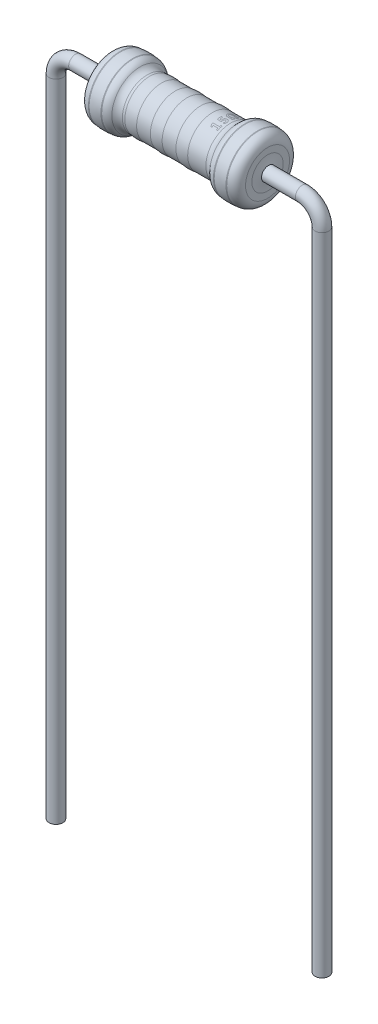
SolidWorks part; units mm, degrees
material "Plain Carbon Steel"
ref_plane "Front Plane" through (0, 0, 0) normal (0, 0, 1) x (1, 0, 0)
ref_plane "Top Plane" through (0, 0, 0) normal (0, 1, 0) x (1, 0, 0)
ref_plane "Right Plane" through (0, 0, 0) normal (1, 0, 0) x (0, 0, -1)
sketch "Sketch1" plane through (0, 0, 0) normal (0, 0, 1) x (1, 0, 0)
  line L0 (-4.33, 0) -> (4.33, 0)
  line L1 (-5.08, -0.75) -> (-5.08, -25.4)
  line L2 (5.08, -0.75) -> (5.08, -25.4)
  line L3 (-5.08, -25.4) -> (5.08, -25.4) construction
  line L4 (0, 0) -> (0, -25.4) construction
  arc A0 (-4.33, 0) -> (-5.08, -0.75) centre (-4.33, -0.75) ccw
  arc A1 (4.33, 0) -> (5.08, -0.75) centre (4.33, -0.75) cw
  dimension "D2" = 0.75
  dimension "D1" = 10.16
  dimension "D3" = 25.4
ref_plane "Plane1" through (-5.08, -25.4, 0) normal (0, -1, 0) x (-1, 0, 0)
sketch "Sketch2" plane through (-5.08, -25.4, 0) normal (0, -1, 0) x (-1, 0, 0)
  circle A0 centre (0, 0) radius 0.265
  dimension "D1" = 0.53
sweep "Sweep1" add profiles "Sketch2" path "Sketch1"
sketch "Sketch3" plane through (0, 0, 0) normal (0, 0, 1) x (1, 0, 0)
  line L0 (-3, 0) -> (3, 0)
  line L5 (-3, 0) -> (-3, 1.2)
  line L6 (3, 0) -> (3, 1.2)
  line L7 (-3, 1.2) -> (-1.8, 1.2)
  line L8 (3, 1.2) -> (1.8, 1.2)
  line L9 (-1.8, 1.2) -> (-1.8, 0.95)
  line L10 (-1.8, 0.95) -> (1.8, 0.95)
  line L11 (1.8, 0.95) -> (1.8, 1.2)
  line L12 (0, 0) -> (0, 0.95) construction
  dimension "D1" = 6
  dimension "D2" = 1.2
  dimension "D3" = 3.6
  dimension "D4" = 0.95
  dimension "D5" = 0.25
revolve "Revolve1" add sketch "Sketch3" angle 360 about L0
fillet "Fillet-1" radius 0.35 2 edges at (1.8, 0, 1.2) (-1.8, 0, 1.2)
fillet "Fillet-2" radius 0.36 4 edges at (3, 0, 1.2) (-3, 0, 1.2) (1.8, 0, 0.95) (-1.8, 0, 0.95)
sketch "Sketch5" plane through (0, 0, 0) normal (0, 0, 1) x (1, 0, 0)
  line L0 (-2.64, -1.2) -> (-2.1354, -1.2) construction
  line L5 (-2.3877, -1.2) -> (-2.3877, 0) construction
  line L10 (-3, 1.2) -> (-1.8, 1.2) construction
  line L15 (-1.05, 0.95) -> (-0.525, 0.95) construction
  line L16 (-3, 0) -> (3, 0) construction
  line L17 (-2.6127, 1.2) -> (-2.1627, 1.2) construction
  line L18 (-2.6127, 1.2) -> (-2.6127, 0) construction
  line L19 (-2.6127, 0) -> (-2.1627, 0) construction
  line L20 (-2.1627, 1.2) -> (-2.1627, 0) construction
  line L21 (-1.8, 0.95) -> (1.8, 0.95) construction
  line L22 (2.6127, 1.2) -> (2.1627, 1.2) construction
  line L23 (2.6127, 1.2) -> (2.6127, 0) construction
  line L24 (2.6127, 0) -> (2.1627, 0) construction
  line L25 (2.1627, 1.2) -> (2.1627, 0) construction
  line L26 (-1.05, 0.95) -> (-1.5, 0.95) construction
  line L27 (-1.05, 0.95) -> (-1.05, 0) construction
  line L28 (-1.05, 0) -> (-1.5, 0) construction
  line L29 (-1.5, 0.95) -> (-1.5, 0) construction
  line L30 (-2.3877, 1.2) -> (-2.3877, 1.22) construction
  line L31 (-0.075, 0.95) -> (-0.525, 0.95) construction
  line L32 (-0.075, 0.95) -> (-0.075, 0) construction
  line L33 (-0.075, 0) -> (-0.525, 0) construction
  line L34 (-0.525, 0.95) -> (-0.525, 0) construction
  line L35 (-1.275, 0.95) -> (-1.275, 0.97) construction
  line L36 (-0.3, 0.95) -> (-0.3, 0.97) construction
  line L37 (2.3877, 1.2) -> (2.3877, 1.22) construction
  line L39 (2.1354, -1.2) -> (2.64, -1.2) construction
  line L41 (2.3877, -1.2) -> (2.3877, 0) construction
  line L44 (3, 1.2) -> (1.8, 1.2) construction
  line L46 (-0.075, 0.95) -> (0.45, 0.95) construction
  line L48 (-3, 0) -> (-3, 0.6)
  line L49 (-3, 0) -> (-3, 1.2) construction
  line L50 (-3, 0) -> (-3.05, 0)
  line L51 (-3.05, 0) -> (-3.05, 0.2)
  line L52 (3, 0) -> (3.05, 0)
  line L53 (3.05, 0) -> (3.05, 0.2)
  line L54 (3, 0) -> (3, 0.6)
  line L55 (3, 0) -> (3, 1.2) construction
  line L56 (-1.05, 0) -> (-0.525, 0) construction
  line L58 (-0.075, 0) -> (0.45, 0) construction
  line L59 (0.45, 0) -> (0.45, 0.95) construction
  line L60 (0.45, 0) -> (0.9, 0) construction
  line L61 (0.9, 0) -> (0.9, 0.95) construction
  line L62 (1.5946, 0.95) -> (-1.5946, 0.95) construction
  line L63 (0.9, 0.95) -> (0.45, 0.95) construction
  line L64 (0.675, 0.95) -> (0.675, 0.97) construction
  arc A0 (-2.6127, 1.2) -> (-2.1627, 1.2) centre (-2.3877, -0.0556) cw construction
  arc A1 (-1.5, 0.95) -> (-1.05, 0.95) centre (-1.275, -0.3056) cw construction
  arc A2 (-0.525, 0.95) -> (-0.075, 0.95) centre (-0.3, -0.3056) cw construction
  arc A3 (2.1627, 1.2) -> (2.6127, 1.2) centre (2.3877, -0.0556) cw construction
  arc A6 (-3, 0.6) -> (-3.05, 0.2) centre (-4.625, 0.6) cw
  arc A7 (3.05, 0.2) -> (3, 0.6) centre (4.625, 0.6) cw
  arc A8 (0.45, 0.95) -> (0.9, 0.95) centre (0.675, -0.3056) cw construction
  dimension "D4" = 0.02
  dimension "D5" = 0.05
  dimension "D7" = 0.6
  dimension "D2" = 1.5
  dimension "D3" = 2.4
  dimension "D1" = 0.45
  dimension "D6" = 0.2
revolve "Revolve Ends" add sketch "Sketch5" angle 360 about L19
sketch "Sketch12" plane through (0, 0, 0) normal (0, 0, 1) x (1, 0, 0)
  line L0 (-2.6127, 0) -> (-2.1627, 0) construction
  line L1 (-2.6127, 0) -> (-2.1627, 0)
  line L2 (-2.6127, 1.2) -> (-2.6127, 0) construction
  line L3 (-2.6127, 1.2) -> (-2.6127, 0)
  line L4 (-2.1627, 1.2) -> (-2.1627, 0) construction
  line L5 (-2.1627, 1.2) -> (-2.1627, 0)
  arc A0 (-2.1627, 1.2) -> (-2.6127, 1.2) centre (-2.3877, -0.0556) ccw construction
  arc A1 (-2.1627, 1.2) -> (-2.6127, 1.2) centre (-2.3877, -0.0556) ccw
revolve "Revolve BAND 1" add sketch "Sketch12" angle 360 about L19
sketch "Sketch7" plane through (0, 0, 0) normal (0, 0, 1) x (1, 0, 0)
  line L0 (-1.05, 0) -> (-1.5, 0) construction
  line L1 (-1.05, 0.95) -> (-1.05, 0) construction
  line L2 (-1.5, 0.95) -> (-1.5, 0) construction
  line L3 (-1.05, 0.95) -> (-1.05, 0)
  line L4 (-1.5, 0.95) -> (-1.5, 0)
  line L5 (-1.05, 0) -> (-1.5, 0)
  arc A0 (-1.05, 0.95) -> (-1.5, 0.95) centre (-1.275, -0.3056) ccw construction
  arc A1 (-1.05, 0.95) -> (-1.5, 0.95) centre (-1.275, -0.3056) ccw
revolve "Revolve BAND 2" add sketch "Sketch7" angle 360 about L28
sketch "Sketch8" plane through (0, 0, 0) normal (0, 0, 1) x (1, 0, 0)
  line L0 (-0.075, 0.95) -> (-0.075, 0) construction
  line L1 (-0.075, 0) -> (-0.525, 0) construction
  line L2 (-0.525, 0.95) -> (-0.525, 0) construction
  line L3 (-0.075, 0.95) -> (-0.075, 0)
  line L4 (-0.075, 0) -> (-0.525, 0)
  line L5 (-0.525, 0.95) -> (-0.525, 0)
  arc A0 (-0.075, 0.95) -> (-0.525, 0.95) centre (-0.3, -0.3056) ccw construction
  arc A1 (-0.075, 0.95) -> (-0.525, 0.95) centre (-0.3, -0.3056) ccw
revolve "Revolve BAND 3" add sketch "Sketch8" angle 360 about L33
sketch "Sketch9" plane through (0, 0, 0) normal (0, 0, 1) x (1, 0, 0)
  line L0 (0.9, 0) -> (0.9, 0.95) construction
  line L1 (0.45, 0) -> (0.45, 0.95) construction
  line L2 (0.45, 0) -> (0.9, 0) construction
  line L3 (0.9, 0) -> (0.9, 0.95)
  line L4 (0.45, 0) -> (0.45, 0.95)
  line L5 (0.45, 0) -> (0.9, 0)
  arc A0 (0.9, 0.95) -> (0.45, 0.95) centre (0.675, -0.3056) ccw construction
  arc A1 (0.9, 0.95) -> (0.45, 0.95) centre (0.675, -0.3056) ccw
revolve "Revolve BAND 4" add sketch "Sketch9" angle 360 about L60
sketch "Sketch11" plane through (0, 0, 0) normal (0, 0, 1) x (1, 0, 0)
  line L0 (2.6127, 1.2) -> (2.6127, 0) construction
  line L1 (2.1627, 1.2) -> (2.1627, 0) construction
  line L2 (2.6127, 0) -> (2.1627, 0) construction
  line L3 (2.6127, 1.2) -> (2.6127, 0)
  line L4 (2.1627, 1.2) -> (2.1627, 0)
  line L5 (2.6127, 0) -> (2.1627, 0)
  arc A0 (2.6127, 1.2) -> (2.1627, 1.2) centre (2.3877, -0.0556) ccw construction
  arc A1 (2.6127, 1.2) -> (2.1627, 1.2) centre (2.3877, -0.0556) ccw
revolve "Revolve5" add sketch "Sketch11" angle 360 about L24
ref_plane "Plane2" through (0, 2, 0) normal (0, 1, 0) x (1, 0, 0)
sketch "Sketch6" plane through (0, 2, 0) normal (0, 1, 0) x (1, 0, 0)
  line L0 (0, 0) -> (1.5, 0) construction
  line L1 (1.5, 1) -> (1.5, -1) construction
  text T0 "15Ω" font "Calibri" height 0.3
  dimension "D1" = 1.5
  dimension "D2" = 2
wrap "Wrap Ohm" sketch "Sketch6" wrap type scribe source sketch "Sketch6" face at (1.5946, 0, 0.95)
